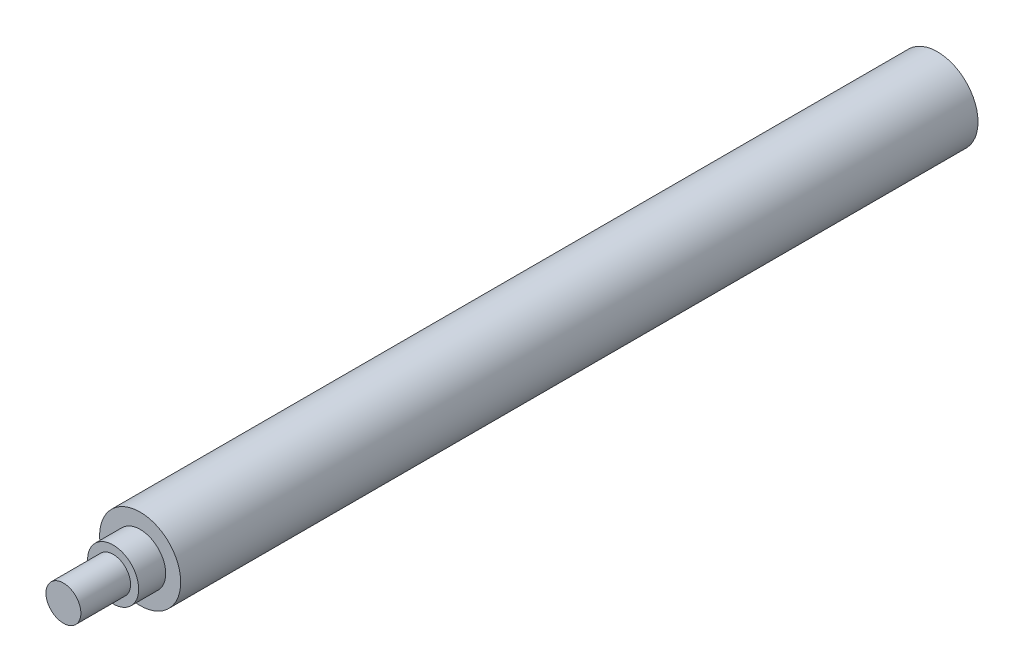
SolidWorks part; units mm, degrees
ref_plane "Front Plane" through (0, 0, 0) normal (0, 0, 1) x (1, 0, 0)
ref_plane "Top Plane" through (0, 0, 0) normal (0, 1, 0) x (1, 0, 0)
ref_plane "Right Plane" through (0, 0, 0) normal (1, 0, 0) x (0, 0, -1)
sketch "Sketch1" plane through (0, 0, 0) normal (0, 1, 0) x (1, 0, 0)
  line L0 (4.7625, 92.075) -> (-4.7625, 92.075) construction
  line L1 (19.505, -10.6045) -> (-19.505, -10.6045) construction
  line L2 (2.05, -1.5875) -> (2.05, -10.6045) construction
  line L3 (19.505, -4.7625) -> (-19.505, -4.7625) construction
  line L4 (3, -1.5875) -> (3, -4.7625) construction
  line L5 (4.7625, -1.5875) -> (-4.7625, -1.5875) construction
  line L6 (0, -1.5875) -> (0, 92.075) construction
  line L7 (4.7625, -1.5875) -> (4.7625, 92.075) construction
  line L8 (4.7625, 92.075) -> (0, 92.075)
  line L9 (2.05, -10.6045) -> (0, -10.6045)
  line L10 (2.05, -4.7625) -> (2.05, -10.6045)
  line L11 (3, -4.7625) -> (2.05, -4.7625)
  line L12 (3, -1.5875) -> (3, -4.7625)
  line L13 (4.7625, -1.5875) -> (3, -1.5875)
  line L14 (0, -10.6045) -> (0, 92.075)
  line L15 (4.7625, -1.5875) -> (4.7625, 92.075)
revolve "Revolve1" add sketch "Sketch1" angle 360 about L14
